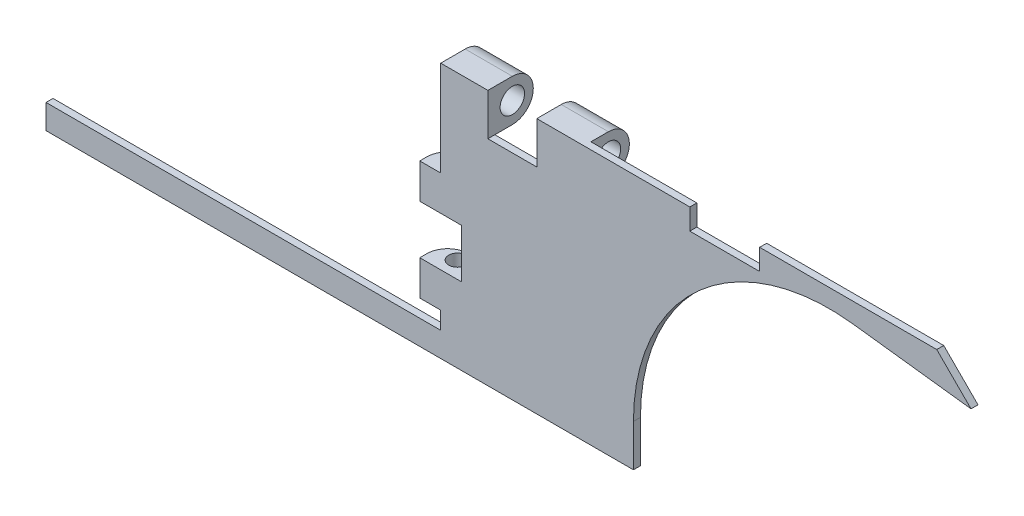
SolidWorks part; units mm, degrees
ref_plane "Front Plane" through (0, 0, 0) normal (0, 0, 1) x (1, 0, 0)
ref_plane "Top Plane" through (0, 0, 0) normal (0, 1, 0) x (1, 0, 0)
ref_plane "Right Plane" through (0, 0, 0) normal (1, 0, 0) x (0, 0, -1)
sketch "Sketch1" plane through (0, 0, 0) normal (0, 0, 1) x (1, 0, 0)
  line L0 (-56.5, -6) -> (27.5877, -6)
  line L1 (76, -6) -> (76, 25.704) construction
  line L2 (76, 30.62) -> (0, 30.62)
  line L3 (0, 30.62) -> (0, -2.5)
  line L4 (0, -2.5) -> (-56.5, -2.5)
  line L5 (-56.5, -2.5) -> (-56.5, -6)
  line L6 (76, 25.704) -> (76, 30.62)
  line L7 (76, 25.704) -> (59, 27.7913)
  line L8 (27.5877, -6) -> (76, -6) construction
  line L9 (27.5877, 0) -> (27.5877, -6)
  arc A0 (59, 27.7913) -> (27.5877, 0) centre (55.5877, 0) ccw
  point P2 (-14.4562, -6)
  dimension "D7" = 7
  dimension "D5" = 6
  dimension "D6" = 28
  dimension "D1" = 36.62
  dimension "D2" = 132.5
  dimension "D3" = 76
  dimension "D4" = 3.5
  dimension "D8" = 17
extrude "Boss-Extrude1" add sketch "Sketch1" along normal mid plane 1 contours L2 L3 L4 L5 L0 L9 A0 L7 L6
ref_plane "Plane1" through (5, 0, 0) normal (-1, 0, 0) x (0, 0, 1)
sketch "Sketch5" plane through (0, 0, 0) normal (0, 1, 0) x (1, 0, 0)
  line L0 (76, 0.5) -> (0, 0.5) construction
  line L1 (0, 0.5) -> (3, 0.5)
  line L3 (0, 0.5) -> (0, -0.5)
  line L4 (0, -0.5) -> (-3, -0.5)
  line L5 (0, 0.5) -> (-56.5, 0.5) construction
  line L6 (0, -0.5) -> (-56.5, -0.5) construction
  line L7 (-3, -0.5) -> (-3, 0.5)
  arc A0 (-3, 0.5) -> (3, 0.5) centre (0, 0.5) cw
  dimension "D1" = 3
extrude "Boss-Extrude6" add sketch "Sketch5" along normal blind 5
sketch "Sketch9" plane through (0, 0, 0) normal (-1, 0, 0) x (0, 0, 1)
  line L1 (-0.5, 30.62) -> (-3, 30.62)
  line L2 (-0.5, 24.62) -> (-3, 24.62)
  line L3 (-0.5, 30.62) -> (-0.5, 5) construction
  line L4 (-0.5, 30.62) -> (-0.5, 24.62)
  arc A0 (-3, 30.62) -> (-3, 24.62) centre (-3, 27.62) cw construction
  arc A1 (-3, 30.62) -> (-3, 24.62) centre (-3, 27.62) ccw
  dimension "D1" = 3
  dimension "D2" = 3.5
extrude "Boss-Extrude5" add sketch "Sketch9" against normal blind 6.75
pattern_linear "LPattern2" count 2 spacing 13.75 along (1, 0, 0) of "Boss-Extrude5"
sketch "Sketch10" plane through (0, 0, 0) normal (-1, 0, 0) x (0, 0, 1)
  circle A0 centre (-3, 27.62) radius 1.75
  arc A4 (-3, 30.62) -> (-3, 24.62) centre (-3, 27.62) ccw construction
  dimension "D1" = 3.5
extrude "Cut-Extrude4" cut sketch "Sketch10" against normal up to surface (20.5 mm away) up to face at (20.5, 27.62, -2.5)
pattern_linear "LPattern3" count 2 spacing 12 along (0, 1, 0) of "Boss-Extrude6"
sketch "Sketch12" plane through (0, 0, 0) normal (0, -1, 0) x (1, 0, 0)
  circle A0 centre (0, -1.9) radius 1.25
  arc A1 (-3, -0.5) -> (3, -0.5) centre (0, -0.5) ccw construction
  dimension "D1" = 2.5
  dimension "D2" = 1.4
extrude "Cut-Extrude5" cut sketch "Sketch12" against normal up to surface (17 mm away) up to face at (-0.6, 17, -0.7)
sketch "Sketch13" plane through (0, 0, -0.5) normal (0, 0, -1) x (-1, 0, 0)
  line L0 (-13.75, 30.62) -> (-13.75, 24.62)
  line L1 (-13.75, 24.62) -> (-13.75, 30.62) construction
  line L2 (-13.75, 24.62) -> (-13.75, 30.62) construction
  line L3 (-13.75, 24.62) -> (-6.75, 24.62)
  line L4 (-6.75, 24.62) -> (-6.75, 30.62)
  line L5 (-6.75, 30.62) -> (-13.75, 30.62)
extrude "Cut-Extrude6" cut sketch "Sketch13" against normal up to surface (1 mm away) up to face at (7.9362, 10.1653, 0.5)
chamfer "Chamfer1" distance 5 angle 45 1 edges at (76, 30.62, 0)
sketch "Sketch15" plane through (0, 0, 0.5) normal (0, 0, 1) x (1, 0, 0)
  line L0 (35.6543, 30.62) -> (35.6543, 27.62)
  line L1 (71, 30.62) -> (13.75, 30.62) construction
  line L2 (35.6543, 27.62) -> (45.6543, 27.62)
  line L3 (45.6543, 27.62) -> (45.6543, 30.62)
  line L4 (45.6543, 30.62) -> (35.6543, 30.62)
  point P4 (40.6543, 27.62)
  dimension "D1" = 3
  dimension "D2" = 10
  dimension "D3" = 35.25
extrude "Cut-Extrude8" cut sketch "Sketch15" against normal up to next
sketch "Sketch16" plane through (0, 0, -0.5) normal (0, 0, -1) x (-1, 0, 0)
  line L0 (0, 12) -> (-3, 12)
  line L1 (-3, 12) -> (-3, 5)
  line L2 (-3, 5) -> (0, 5)
  line L3 (3, 5) -> (-3, 5) construction
  line L4 (0, 5) -> (0, 12)
extrude "Cut-Extrude9" cut sketch "Sketch16" against normal up to next
